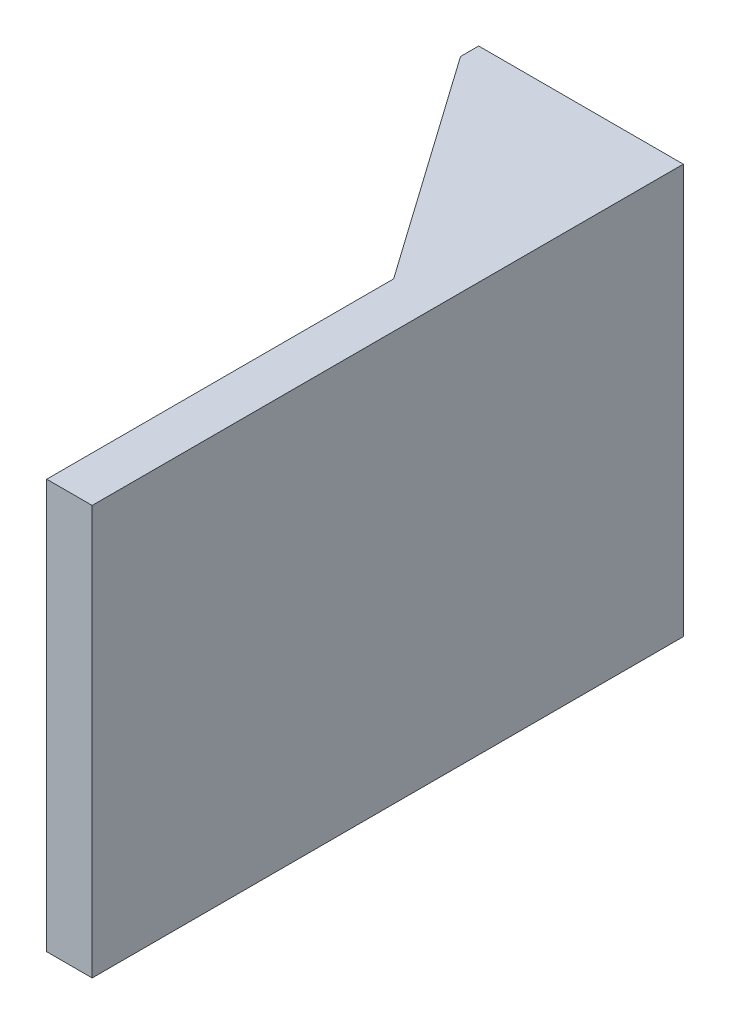
SolidWorks part; units mm, degrees
ref_plane "Front Plane" through (0, 0, 0) normal (0, 0, 1) x (1, 0, 0)
ref_plane "Top Plane" through (0, 0, 0) normal (0, 1, 0) x (1, 0, 0)
ref_plane "Right Plane" through (0, 0, 0) normal (1, 0, 0) x (0, 0, -1)
sketch "Sketch1" plane through (0, 0, 0) normal (0, 1, 0) x (1, 0, 0)
  line L1 (15.5567, 33.0644) -> (15.5567, -31.9356)
  line L2 (15.5567, -31.9356) -> (10.5567, -31.9356)
  line L3 (10.5567, -31.9356) -> (10.5567, 31.0644)
  line L5 (-6.9433, 33.0644) -> (15.5567, 33.0644)
  line L8 (-6.9433, 33.0644) -> (-6.9433, 31.0644)
  line L9 (-6.9433, 31.0644) -> (10.5567, 31.0644)
  line L10 (-6.9433, 31.0644) -> (10.5567, 6.2102)
  point P2 (0, 0)
  dimension "D1" = 5
  dimension "D2" = 65
  dimension "D3" = 63
  dimension "D4" = 22.5
extrude "Boss-Extrude1" add sketch "Sketch1" along normal blind 5 contours L9 L10 L3 | L8 L9 L3 L2 L1 L5 region at (11.963, 0, -3.6269) region at (4.7234, 0, -22.7797)
extrude "Boss-Extrude2" add sketch "Sketch1<3>" against normal blind 40 contours L8 L9 L3 L2 L1 L5 region at (11.963, 0, -3.6269)
sketch "Sketch1<3>" plane through (0, 0, 0) normal (0, 1, 0) x (1, 0, 0) same geometry as "Sketch1"
